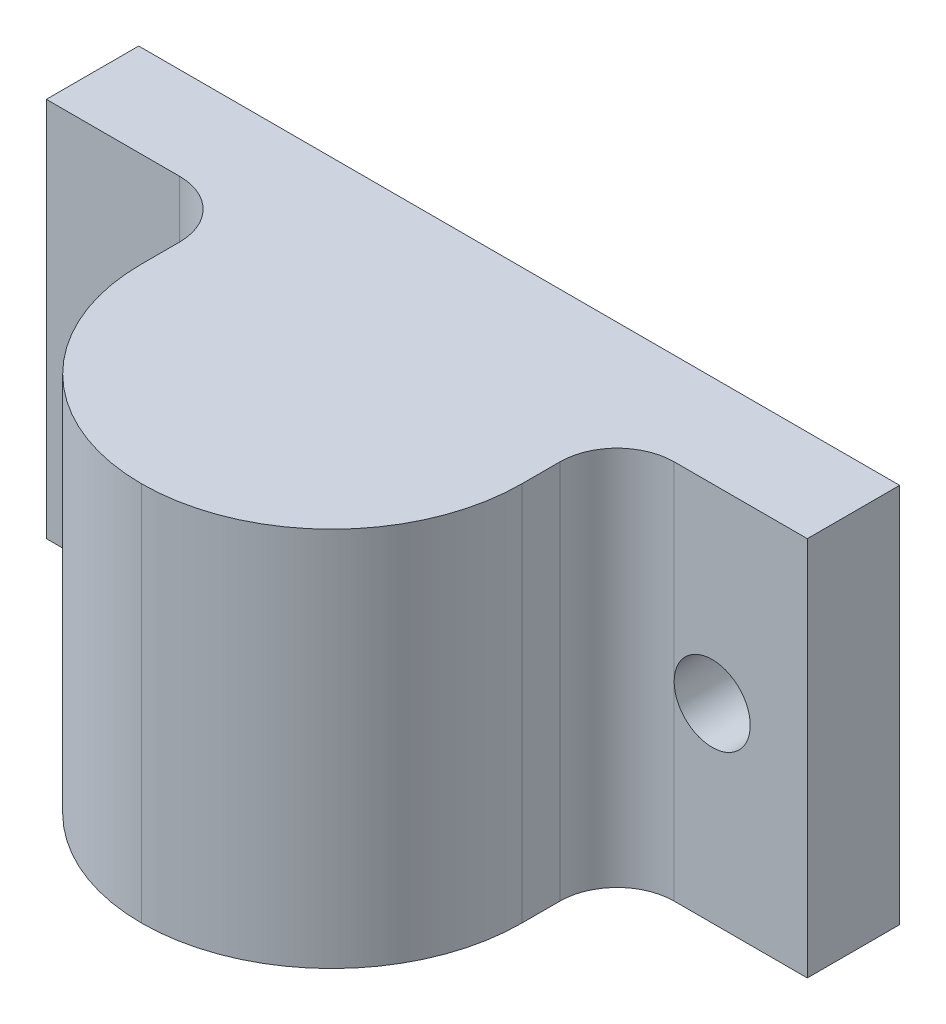
SolidWorks part; units mm, degrees
ref_plane "Front Plane" through (0, 0, 0) normal (0, 0, 1) x (1, 0, 0)
ref_plane "Top Plane" through (0, 0, 0) normal (0, 1, 0) x (1, 0, 0)
ref_plane "Right Plane" through (0, 0, 0) normal (1, 0, 0) x (0, 0, -1)
sketch "Sketch6" plane through (0, 0, 0) normal (0, 0, 1) x (1, 0, 0)
  line L1 (-20, 10) -> (20, 10)
  line L2 (-20, 10) -> (-20, -10)
  line L3 (-20, -10) -> (20, -10)
  line L4 (20, 10) -> (20, -10)
  line L5 (-20, 10) -> (20, -10) construction
  line L6 (-20, -10) -> (20, 10) construction
  point P0 (0, 0)
  dimension "D1" = 40
  dimension "D2" = 20
extrude "Boss-Extrude3" add sketch "Sketch6" along normal blind 19.8548
sketch "Sketch9" plane through (0, 0, 19.8548) normal (0, 0, 1) x (1, 0, 0)
  line L0 (-20, -10) -> (20, -10) construction
  line L1 (-20, 10) -> (-10, 10)
  line L2 (-20, 10) -> (-20, -10)
  line L3 (-20, -10) -> (-10, -10)
  line L4 (-10, 10) -> (-10, -10)
  line L6 (20, 10) -> (10, 10)
  line L7 (20, 10) -> (20, -10)
  line L8 (20, -10) -> (10, -10)
  line L9 (10, 10) -> (10, -10)
  dimension "D1" = 10
  dimension "D2" = 10
extrude "Cut-Extrude6" cut sketch "Sketch9" against normal blind 15
sketch "Sketch10" plane through (0, -10, 0) normal (0, -1, 0) x (1, 0, 0)
  circle A0 centre (0, 12.5) radius 4
extrude "Cut-Extrude7" cut sketch "Sketch10" against normal blind 15
sketch "Sketch11" plane through (0, 0, 4.8548) normal (0, 0, 1) x (1, 0, 0)
  circle A0 centre (-15, 0) radius 2
  circle A1 centre (15, 0) radius 2
extrude "Cut-Extrude8" cut sketch "Sketch11" against normal blind 5
fillet "Fillet1" radius 10 1 edges at (10, 0, 19.8548)
fillet "Fillet2" radius 10 1 edges at (-10, 0, 19.8548)
fillet "Fillet5" radius 3 2 edges at (-10, 0, 4.8548) (10, 0, 4.8548)
